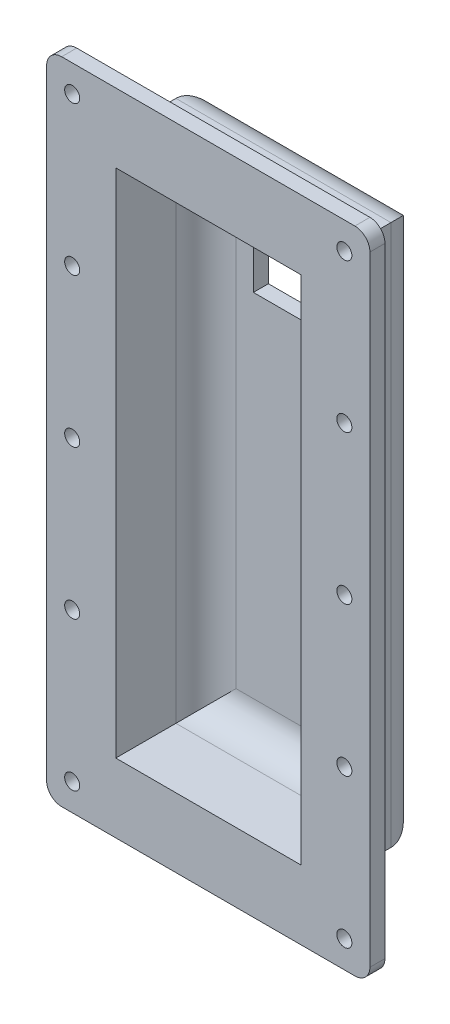
SolidWorks part; units mm, degrees
ref_plane "Front Plane" through (0, 0, 0) normal (0, 0, 1) x (1, 0, 0)
ref_plane "Top Plane" through (0, 0, 0) normal (0, 1, 0) x (1, 0, 0)
ref_plane "Right Plane" through (0, 0, 0) normal (1, 0, 0) x (0, 0, -1)
sketch "Sketch1" plane through (0, 0, 0) normal (0, 0, 1) x (1, 0, 0)
  line L1 (-17.88, 45) -> (17.88, 45)
  line L2 (-17.88, 45) -> (-17.88, -45)
  line L3 (-17.88, -45) -> (17.88, -45)
  line L4 (17.88, 45) -> (17.88, -45)
  line L5 (-17.88, 45) -> (17.88, -45) construction
  line L6 (-17.88, -45) -> (17.88, 45) construction
  point P0 (0, 0)
  dimension "D1" = 35.76
  dimension "D2" = 90
extrude "Boss-Extrude1" add sketch "Sketch1" along normal blind 15
sketch "Sketch2" plane through (0, 0, 15) normal (0, 0, 1) x (1, 0, 0)
  line L0 (-17.88, 45) -> (17.88, 45) construction
  line L1 (-26.88, 54) -> (26.88, 54)
  line L2 (-26.88, 54) -> (-26.88, -54)
  line L3 (-26.88, -54) -> (26.88, -54)
  line L4 (26.88, 54) -> (26.88, -54)
  line L5 (-26.88, 54) -> (26.88, -54) construction
  line L6 (-26.88, -54) -> (26.88, 54) construction
  line L7 (-17.88, 45) -> (-17.88, -45) construction
  point P0 (0, 0)
  point P8 (0, 45)
  dimension "D1" = 9
  dimension "D2" = 9
extrude "Boss-Extrude2" add sketch "Sketch2" along normal blind 2.5
shell "Shell1" thickness 2.5 removed face at (0, 0, 17.5)
fillet "Fillet1" radius 2.5 4 edges at (-26.88, -54, 16.25) (26.88, -54, 16.25) (26.88, 54, 16.25) (-26.88, 54, 16.25)
fillet "Fillet2" radius 5 8 edges at (0, -42.5, 2.5) (15.38, 0, 2.5) (-15.38, 0, 2.5) (0, 42.5, 2.5) (0, -45, 0) (17.88, 0, 0) (0, 45, 0) (-17.88, 0, 0)
sketch "Sketch3" plane through (0, 0, 2.5) normal (0, 0, 1) x (1, 0, 0)
  line L1 (-7.5, 29) -> (7.5, 29)
  line L2 (-7.5, 29) -> (-7.5, 21)
  line L3 (-7.5, 21) -> (7.5, 21)
  line L4 (7.5, 29) -> (7.5, 21)
  line L5 (-7.5, 29) -> (7.5, 21) construction
  line L6 (-7.5, 21) -> (7.5, 29) construction
  point P0 (0, 25)
  dimension "D1" = 8
  dimension "D2" = 15
  dimension "D3" = 25
extrude "Cut-Extrude1" cut sketch "Sketch3" against normal through all
sketch "Sketch4" plane through (0, 0, 17.5) normal (0, 0, 1) x (1, 0, 0)
  line L0 (17.88, 45) -> (17.88, -45) construction
  line L3 (-22.63, -49.5) -> (22.63, -49.5) construction
  line L10 (-22.63, -49.5) -> (-22.63, 49.5) construction
  line L11 (-22.63, 49.5) -> (22.63, 49.5) construction
  line L12 (22.63, -49.5) -> (22.63, 49.5) construction
  line L13 (-22.63, -49.5) -> (22.63, 49.5) construction
  line L14 (-22.63, 49.5) -> (22.63, -49.5) construction
  circle A16 centre (-22.63, 49.5) radius 1.25
  circle A17 centre (22.63, 49.5) radius 1.25
  circle A18 centre (22.63, 24.75) radius 1.25
  circle A19 centre (22.63, 0) radius 1.25
  circle A20 centre (22.63, -24.75) radius 1.25
  circle A21 centre (22.63, -49.5) radius 1.25
  circle A22 centre (-22.63, 24.75) radius 1.25
  circle A23 centre (-22.63, 0) radius 1.25
  circle A24 centre (-22.63, -24.75) radius 1.25
  circle A25 centre (-22.63, -49.5) radius 1.25
  point P0 (0, 0)
  point P9 (27.9117, -49.5)
  point P10 (0, 0)
  point P18 (0, 0)
  dimension "D1" = 99
  dimension "D3" = 2.5
  dimension "D2" = 4.75
  dimension "D4" = 5
extrude "Cut-Extrude2" cut sketch "Sketch4" against normal up to surface (2.5 mm away) up to face at (0, 0, 15)
equation "\"case_width\"=35.76"
equation "\"D1@Sketch1\"=\"case_width\""
